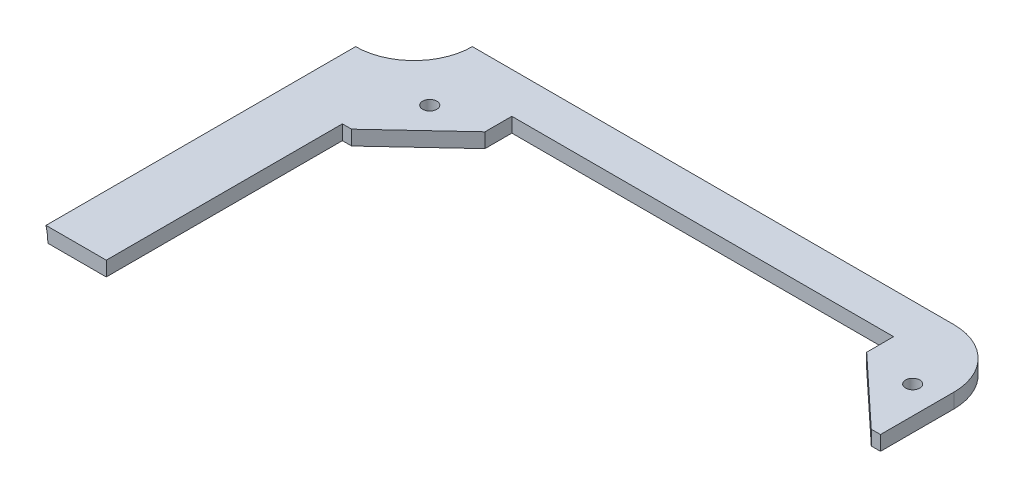
SolidWorks part; units mm, degrees
material "AISI 4130 Steel, annealed at 865C"
ref_plane "X-Y Datum" through (0, 0, 0) normal (0, 0, 1) x (1, 0, 0)
ref_plane "X-Z Datum" through (0, 0, 0) normal (0, 1, 0) x (1, 0, 0)
ref_plane "Y-Z Datum" through (0, 0, 0) normal (1, 0, 0) x (0, 0, -1)
sketch "Sketch1" plane through (0, 0, 0) normal (0, 1, 0) x (1, 0, 0)
  line L1 (-95.25, -38.1) -> (95.25, -38.1)
  line L2 (-95.25, -38.1) -> (-95.25, 38.1)
  line L3 (-95.25, 38.1) -> (95.25, 38.1)
  line L4 (95.25, -38.1) -> (95.25, 38.1)
  line L5 (-95.25, -38.1) -> (95.25, 38.1) construction
  line L6 (-95.25, 38.1) -> (95.25, -38.1) construction
  point P0 (0, 0)
  dimension "D1" = 190.5
  dimension "D2" = 76.2
extrude "Boss-Extrude1" add sketch "Sketch1" along normal blind 3.175 contours L3 L4 L1 L2
sketch "Sketch2" plane through (0, 3.175, 0) normal (0, 1, 0) x (1, 0, 0)
  line L0 (-56.5, 13.235) -> (-41.5, 27.235) construction
  line L1 (-41.5, 27.235) -> (-41.5, 33.085) construction
  line L2 (-41.5, 33.085) -> (41.5, 33.085) construction
  line L3 (41.5, 33.085) -> (41.5, 27.235) construction
  line L4 (-95.25, 38.1) -> (-95.25, -38.1)
  line L5 (-95.25, -38.1) -> (95.25, -38.1)
  line L6 (95.25, -38.1) -> (95.25, 38.1)
  line L7 (95.25, 38.1) -> (-95.25, 38.1)
  line L8 (-95.25, 38.1) -> (-95.25, -38.1)
  line L9 (-95.25, -38.1) -> (95.25, -38.1)
  line L10 (95.25, -38.1) -> (95.25, 38.1)
  line L11 (95.25, 38.1) -> (-95.25, 38.1)
  line L12 (41.5, 27.235) -> (56.5, 13.235) construction
  line L13 (-56.5, 13.235) -> (-41.5, 27.235)
  line L14 (-41.5, 27.235) -> (-41.5, 33.085)
  line L15 (-41.5, 33.085) -> (41.5, 33.085)
  line L16 (41.5, 33.085) -> (41.5, 27.235)
  line L17 (41.5, 27.235) -> (56.5, 13.235)
  line L18 (56.5, 13.235) -> (95.25, 13.235)
  line L19 (-56.5, 13.235) -> (-58.5, 13.235)
  line L20 (58.5, -451.265) -> (58.5, 38.735) construction
  line L21 (58.5, 13.235) -> (58.5, 38.735)
  line L22 (-58.5, 38.735) -> (-58.5, -451.265) construction
  line L23 (-58.5, 38.735) -> (-58.5, -38.1)
  circle A0 centre (-52.5052, 26.2402) radius 1.5453 construction
  circle A1 centre (52.5, 26.2402) radius 1.5453 construction
  circle A2 centre (-52.5052, 26.2402) radius 1.5453
  circle A3 centre (52.5, 26.2402) radius 1.5453
  line M6 (-95.25, -38.1) -> (95.25, -38.1)
  line M7 (95.25, -38.1) -> (95.25, 38.1)
  line M8 (95.25, 38.1) -> (-95.25, 38.1)
  dimension "D1" = 0
extrude "Cut-Extrude4" cut sketch "Sketch2" against normal through all contours L13 L19 L8 L18 L17 L16 L15 L14 M6 M7 | L21 L18 L10 M8 | A2 | A3 | A2 region at (14.8743, 3.175, 5.765) region at (76.875, 3.175, -25.6675) region at (-52.5052, 3.175, -26.2402) region at (52.5, 3.175, -26.2402)
sketch "Sketch3" plane through (0, 0, -38.1) normal (0, 0, -1) x (-1, 0, 0)
  line L4 (95.25, 3.175) -> (-58.5, 3.175)
  line L5 (-58.5, 3.175) -> (-58.5, 0)
  line L6 (-58.5, 0) -> (95.25, 0)
  line L7 (95.25, 0) -> (95.25, 3.175)
  line L8 (95.25, 3.175) -> (-58.5, 3.175)
  line L9 (-58.5, 3.175) -> (-58.5, 0)
  line L10 (-58.5, 0) -> (95.25, 0)
  line L11 (95.25, 0) -> (95.25, 3.175)
  dimension "D1" = 0
extrude "Boss-Extrude2" add sketch "Sketch3" along normal blind 3.81
sketch "Sketch6" plane through (0, 0, 0) normal (0, -1, 0) x (1, 0, 0)
  line L0 (58.5, -41.91) -> (-95.25, -41.91) construction
  line L1 (58.5, -41.91) -> (-95.25, -41.91) construction
  line L14 (58.5, -38.735) -> (-95.25, -38.735) construction
  dimension "D1" = 3.175
sketch "Sketch7" plane through (0, 3.175, 0) normal (0, 1, 0) x (1, 0, 0)
  line L2 (-95.25, 38.735) -> (58.5, 38.735)
  line L3 (-95.25, 38.735) -> (58.5, 38.735) construction
  dimension "D1" = 3.175
sketch3d "3DSketch6"
  line L0 (-83.9, 0, -54.7189) -> (-83.9, 0, 449.8196)
sweep "Cut-Sweep1" cut path "3DSketch6" circular profile diameter 25.4 parameters "D3"=25.4
sketch "Sketch9" plane through (0, 3.175, 0) normal (0, 1, 0) x (1, 0, 0)
  line L0 (-71.6033, 41.91) -> (58.5, 41.91) construction
  line L1 (-71.6033, 41.91) -> (-71.6033, -38.1) construction
  line L2 (-71.6033, 29.21) -> (-71.6033, 41.91)
  line L3 (-71.6033, 41.91) -> (-58.9033, 41.91)
  arc A0 (-58.9033, 41.91) -> (-71.6033, 29.21) centre (-71.6033, 41.91) cw
  dimension "D1" = 12.7
extrude "Cut-Extrude5" cut sketch "Sketch9" against normal through all
fillet "Fillet1" radius 12.7 1 edges at (58.5, 1.5875, -41.91)
